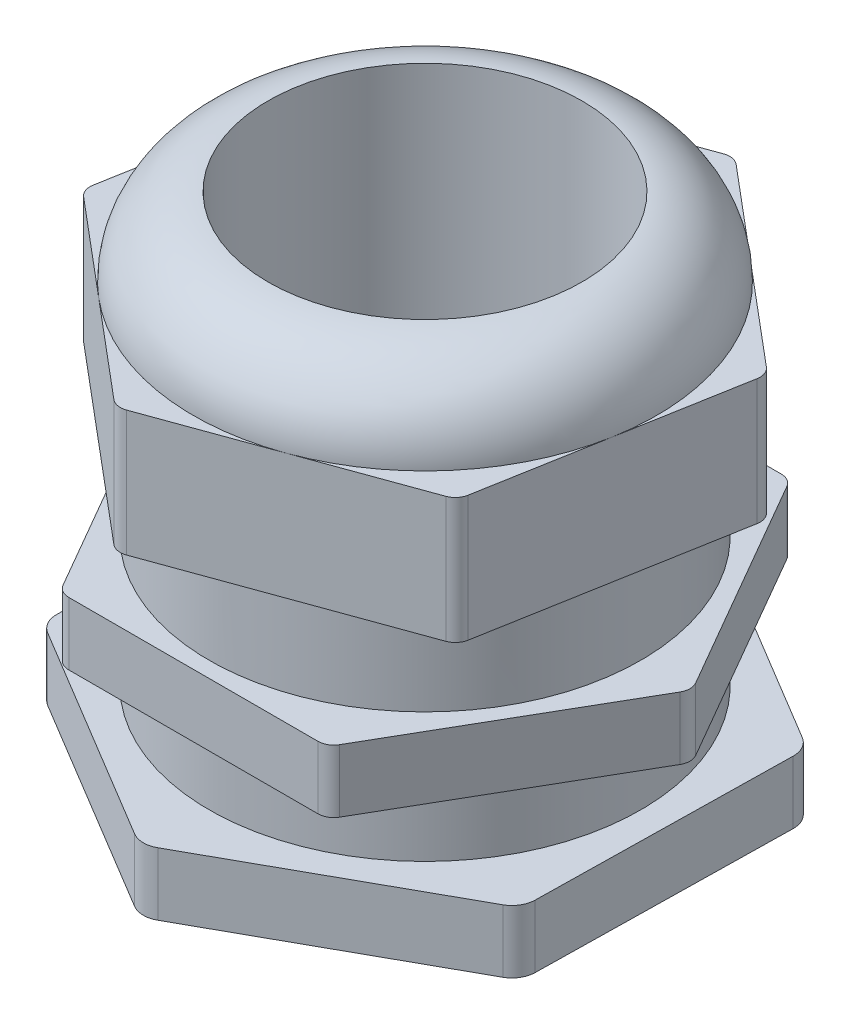
SolidWorks part; units mm, degrees
material "ABS PC"
ref_plane "Спереди" through (0, 0, 0) normal (0, 0, 1) x (1, 0, 0)
ref_plane "Сверху" through (0, 0, 0) normal (0, 1, 0) x (1, 0, 0)
ref_plane "Справа" through (0, 0, 0) normal (1, 0, 0) x (0, 0, -1)
sketch "Эскиз1" plane through (0, 0, 0) normal (0, 1, 0) x (1, 0, 0)
  line L1 (34.0637, 0) -> (17.0318, 29.5)
  line L2 (17.0318, 29.5) -> (-17.0318, 29.5)
  line L3 (-17.0318, 29.5) -> (-34.0637, 0)
  line L4 (-34.0637, 0) -> (-17.0318, -29.5)
  line L5 (-17.0318, -29.5) -> (17.0318, -29.5)
  line L6 (17.0318, -29.5) -> (34.0637, 0)
  circle A0 centre (0, 0) radius 29.5 construction
  dimension "D1" = 59
extrude "Вытянуть1" add sketch "Эскиз1" along normal blind 8
sketch "Эскиз2" plane through (0, 8, 0) normal (0, 1, 0) x (1, 0, 0)
  circle A0 centre (0, 0) radius 27.5
  dimension "D1" = 55
extrude "Вытянуть2" add sketch "Эскиз2" along normal blind 12
sketch "Эскиз3" plane through (0, 20, 0) normal (0, 1, 0) x (1, 0, 0)
  line L1 (5.9572, 33.5387) -> (-26.0668, 21.9284)
  line L2 (-26.0668, 21.9284) -> (-32.024, -11.6103)
  line L3 (-32.024, -11.6103) -> (-5.9572, -33.5387)
  line L4 (-5.9572, -33.5387) -> (26.0668, -21.9284)
  line L5 (26.0668, -21.9284) -> (32.024, 11.6103)
  line L6 (32.024, 11.6103) -> (5.9572, 33.5387)
  circle A0 centre (0, 0) radius 29.5 construction
  dimension "D1" = 59
extrude "Вытянуть3" add sketch "Эскиз3" along normal blind 16
sketch "Эскиз4" plane through (0, 36, 0) normal (0, 1, 0) x (1, 0, 0)
  circle A0 centre (0, 0) radius 29.5
  dimension "D1" = 59
extrude "Вытянуть4" add sketch "Эскиз4" along normal blind 10
fillet "Скругление1" radius 10 1 edges at (0, 46, 29.5)
sketch "Эскиз5" plane through (0, 0, 0) normal (0, -1, 0) x (1, 0, 0)
  circle A0 centre (0, 0) radius 27.5
  dimension "D1" = 55
extrude "Вытянуть5" add sketch "Эскиз5" along normal blind 8.5
sketch "Эскиз6" plane through (0, -8.5, 0) normal (0, -1, 0) x (1, 0, 0)
  line L1 (30.6904, 18.4238) -> (-0.6103, 35.7905)
  line L2 (-0.6103, 35.7905) -> (-31.3006, 17.3667)
  line L3 (-31.3006, 17.3667) -> (-30.6904, -18.4238)
  line L4 (-30.6904, -18.4238) -> (0.6103, -35.7905)
  line L5 (0.6103, -35.7905) -> (31.3006, -17.3667)
  line L6 (31.3006, -17.3667) -> (30.6904, 18.4238)
  circle A0 centre (0, 0) radius 31 construction
  dimension "D1" = 62
extrude "Вытянуть6" add sketch "Эскиз6" along normal blind 8
sketch "Эскиз7" plane through (0, 46, 0) normal (0, 1, 0) x (1, 0, 0)
  circle A0 centre (0, 0) radius 20
  dimension "D1" = 40
extrude "Вырез-Вытянуть1" cut sketch "Эскиз7" against normal through all
fillet "Скругление2" radius 2 6 edges at (-32.024, 28, 11.6103) (-5.9572, 28, 33.5387) (26.0668, 28, 21.9284) (32.024, 28, -11.6103) (-26.0668, 28, -21.9284) (5.9572, 28, -33.5387)
fillet "Скругление3" radius 2 6 edges at (17.0318, 4, 29.5) (34.0637, 4, 0) (17.0318, 4, -29.5) (-17.0318, 4, 29.5) (-34.0637, 4, 0) (-17.0318, 4, -29.5)
fillet "Скругление4" radius 3 6 edges at (-0.6103, -12.5, 35.7905) (-31.3006, -12.5, 17.3667) (-30.6904, -12.5, -18.4238) (0.6103, -12.5, -35.7905) (31.3006, -12.5, -17.3667) (30.6904, -12.5, 18.4238)
